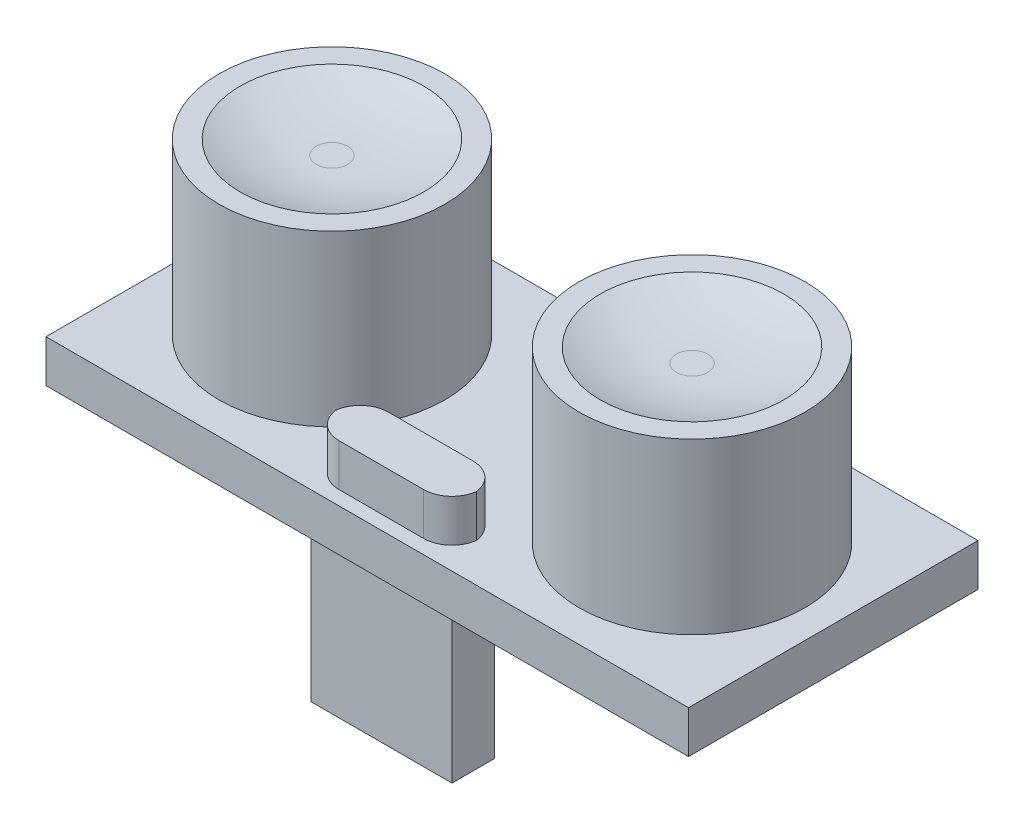
SolidWorks part; units mm, degrees
ref_plane "Front" through (0, 0, 0) normal (0, 0, 1) x (1, 0, 0)
ref_plane "Top" through (0, 0, 0) normal (0, 1, 0) x (1, 0, 0)
ref_plane "Right" through (0, 0, 0) normal (1, 0, 0) x (0, 0, -1)
sketch "Sketch1" plane through (0, 0, 0) normal (0, 1, 0) x (1, 0, 0)
  line L1 (0, 0) -> (45.5, 0)
  line L2 (0, 0) -> (0, 20.5)
  line L3 (0, 20.5) -> (45.5, 20.5)
  line L4 (45.5, 0) -> (45.5, 20.5)
  dimension "D1" = 45.5
  dimension "D2" = 20.5
extrude "Boss-Extrude1" add sketch "Sketch1" along normal blind 3
sketch "Sketch2" plane through (0, 3, 0) normal (0, 1, 0) x (1, 0, 0)
  line L0 (45.5, 20.5) -> (0, 20.5) construction
  line L2 (0, 20.5) -> (0, 0) construction
  line L3 (45.5, 0) -> (45.5, 20.5) construction
  circle A0 centre (10, 10.25) radius 8
  circle A1 centre (35.5, 10.25) radius 8
  point P8 (0, 0)
  dimension "D1" = 16
  dimension "D2" = 10.25
  dimension "D3" = 10
  dimension "D4" = 10
extrude "Boss-Extrude2" add sketch "Sketch2" along normal blind 12
sketch "Sketch3" plane through (0, 0, 0) normal (0, -1, 0) x (1, 0, 0)
  line L0 (0, 0) -> (45.5, 0) construction
  line L1 (17.75, -1) -> (27.75, -1)
  line L2 (17.75, -1) -> (17.75, -4)
  line L3 (17.75, -4) -> (27.75, -4)
  line L4 (27.75, -1) -> (27.75, -4)
  line L5 (0, -20.5) -> (0, 0) construction
  dimension "D1" = 10
  dimension "D2" = 3
  dimension "D3" = 1
  dimension "D4" = 17.75
extrude "Boss-Extrude3" add sketch "Sketch3" along normal blind 11
sketch "Sketch4" plane through (0, 15, 0) normal (0, 1, 0) x (1, 0, 0)
  circle A0 centre (10, 10.25) radius 6.5
  circle A1 centre (35.5, 10.25) radius 6.5
  dimension "D1" = 13
extrude "Cut-Extrude1" cut sketch "Sketch4" against normal blind 1
fillet "Fillet1" radius 15 2 edges at (35.5, 14, -3.75) (10, 14, -3.75)
sketch "Sketch5" plane through (0, 3, 0) normal (0, 1, 0) x (1, 0, 0)
  line L0 (0, 20.5) -> (0, 0) construction
  line L1 (17.75, 4.5) -> (27.75, 4.5)
  line L2 (17.75, 4.5) -> (17.75, 1)
  line L3 (17.75, 1) -> (27.75, 1)
  line L4 (27.75, 4.5) -> (27.75, 1)
  line L5 (45.5, 20.5) -> (0, 20.5) construction
  dimension "D1" = 10
  dimension "D2" = 3.5
  dimension "D3" = 17.75
  dimension "D4" = 16
extrude "Boss-Extrude4" add sketch "Sketch5" along normal blind 3
fillet "Fillet2" radius 2 4 edges at (17.75, 4.5, -1) (17.75, 4.5, -4.5) (27.75, 4.5, -1) (27.75, 4.5, -4.5)
